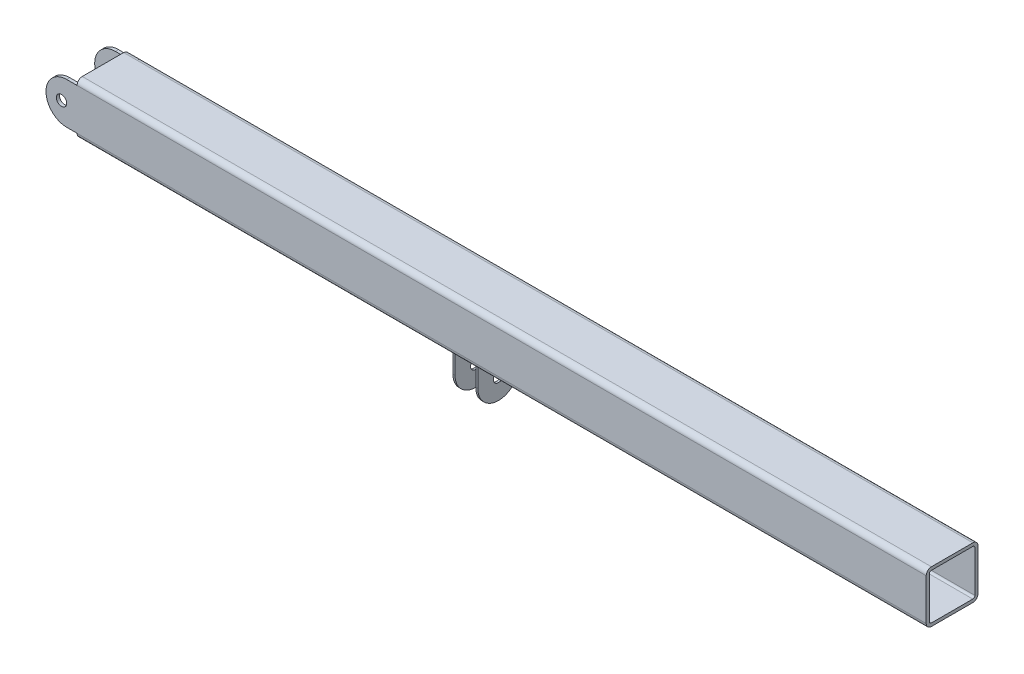
SolidWorks part; units mm, degrees
ref_plane "Front Plane" through (0, 0, 0) normal (0, 0, 1) x (1, 0, 0)
ref_plane "Top Plane" through (0, 0, 0) normal (0, 1, 0) x (1, 0, 0)
ref_plane "Right Plane" through (0, 0, 0) normal (1, 0, 0) x (0, 0, -1)
sketch "Sketch1" plane through (0, 0, 0) normal (1, 0, 0) x (0, 0, -1)
  line L1 (-20, -25) -> (20, -25)
  line L2 (-25, -20) -> (-25, 20)
  line L3 (-20, 25) -> (20, 25)
  line L4 (25, -20) -> (25, 20)
  line L5 (-25, -25) -> (25, 25) construction
  line L6 (-25, 25) -> (25, -25) construction
  arc A0 (-20, -25) -> (-25, -20) centre (-20, -20) cw
  arc A1 (20, -25) -> (25, -20) centre (20, -20) ccw
  arc A2 (20, 25) -> (25, 20) centre (20, 20) cw
  arc A3 (-25, 20) -> (-20, 25) centre (-20, 20) cw
  point P0 (0, 0)
  dimension "D3" = 5
  dimension "D1" = 50
  dimension "D2" = 50
extrude "Extrude-Thin1" add sketch "Sketch1" along normal blind 820 thin thin type one direction reverse wall 3
sketch "Sketch3" plane through (0, 0, -25) normal (0, 0, -1) x (-1, 0, 0)
  line L0 (0, 20) -> (10, 20)
  line L1 (0, -20) -> (10, -20)
  line L2 (0, -20) -> (0, 20) construction
  line L3 (0, -20) -> (0, 20)
  arc A0 (10, 20) -> (10, -20) centre (10, 0) cw
  circle A1 centre (15, 0) radius 5
  dimension "D1" = 10
extrude "Boss-Extrude2" add sketch "Sketch3" against normal up to surface (3 mm away) up to face at (410, 0, -22)
extrude "Boss-Extrude3" add sketch "Sketch3<3>" against normal up to surface (50 mm away) from surface up to face at (410, 0, 25) starting at face at (410, 0, 22)
sketch "Sketch3<3>" plane through (0, 0, -25) normal (0, 0, -1) x (-1, 0, 0) same geometry as "Sketch3"
sketch "Sketch5" plane through (0, -25, 0) normal (0, -1, 0) x (1, 0, 0)
  line L1 (358, -20) -> (358.0025, 20)
  line L2 (820, 20) -> (820, -20) construction
  line L3 (820, 25) -> (0, 25) construction
  line L4 (360, 20) -> (358.0025, 20)
  line L5 (360, -20) -> (358, -20)
  line L9 (380, 20) -> (381.9975, 20)
  line L10 (382, -20) -> (381.9975, 20)
  line L11 (380, -20) -> (382, -20)
  line L12 (380, -20) -> (380, 20)
  line L13 (360, -20) -> (360, 20)
  line L14 (335, -20) -> (335, 20) construction
  dimension "D1" = 20
  dimension "D2" = 440
  dimension "D3" = 2
  dimension "D4" = 2
  dimension "D5" = 5
  dimension "D6" = 5
  dimension "D7" = 40
  dimension "D8" = 40
  dimension "D9" = 40
  dimension "D10" = 40
extrude "Boss-Extrude4" add sketch "Sketch5" along normal blind 40 and the other way blind 10
fillet "Fillet1" radius 20 4 edges at (380.9988, -65, 20) (381, -65, -20) (359.0012, -65, 20) (359, -65, -20)
sketch "Sketch7" plane through (381.9988, 0, 0.0238) normal (1, 0, 0.0001) x (0.0001, 0, -1)
  circle A0 centre (0.0238, -45) radius 5
  arc A1 (-19.9762, -45) -> (0.0238, -65) centre (0.0238, -45) ccw construction
  dimension "D1" = 10
extrude "Cut-Extrude3" cut sketch "Sketch7" against normal through all contours A0
